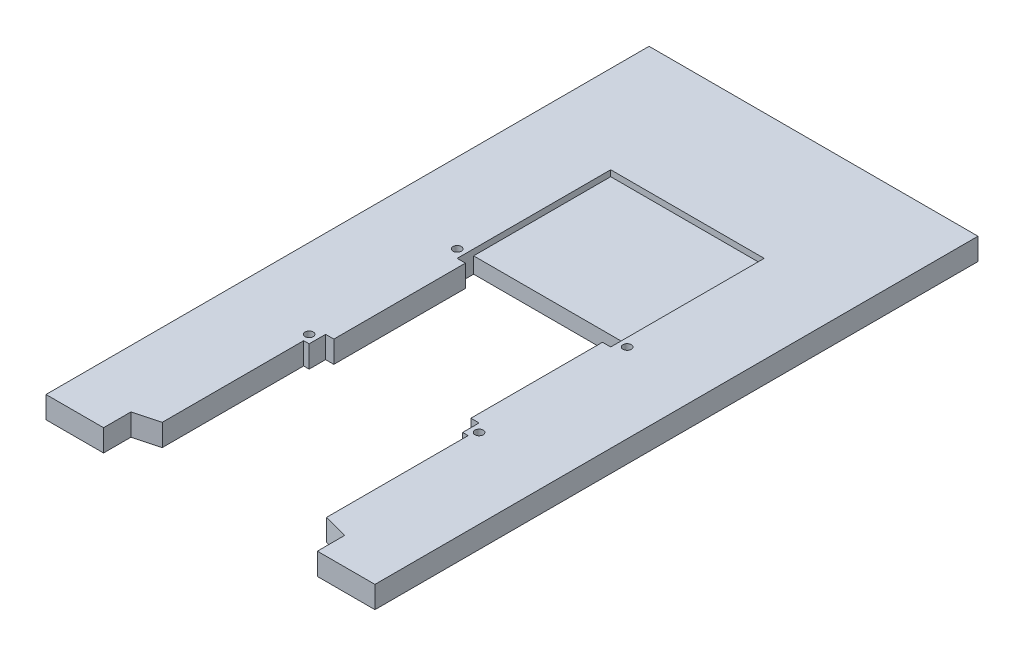
SolidWorks part; units mm, degrees
ref_plane "Front Plane" through (0, 0, 0) normal (0, 0, 1) x (1, 0, 0)
ref_plane "Top Plane" through (0, 0, 0) normal (0, 1, 0) x (1, 0, 0)
ref_plane "Right Plane" through (0, 0, 0) normal (1, 0, 0) x (0, 0, -1)
sketch "Sketch1" plane through (0, 0, 0) normal (0, 1, 0) x (1, 0, 0)
  line L1 (-30, 12.4115) -> (-30, 64)
  line L2 (-28, 124) -> (28, 124)
  line L3 (30, 64) -> (30, 12.4115)
  line L6 (-60, 0) -> (-39, 0)
  line L8 (-28, 70) -> (-28, 64)
  line L9 (-28, 64) -> (-30, 64)
  line L10 (28, 70) -> (28, 64)
  line L11 (28, 64) -> (30, 64)
  line L12 (-28, 70) -> (-25, 70)
  line L13 (-25, 70) -> (-25, 118)
  line L14 (-25, 118) -> (-28, 118)
  line L15 (-28, 118) -> (-28, 124)
  line L16 (28, 124) -> (28, 118)
  line L17 (28, 118) -> (25, 118)
  line L18 (25, 118) -> (25, 70)
  line L19 (25, 70) -> (28, 70)
  line L20 (-39, 0) -> (-39, 10)
  line L21 (-39, 10) -> (-30, 12.4115)
  line L22 (39, 0) -> (39, 10)
  line L23 (39, 10) -> (30, 12.4115)
  line L24 (-60, 0) -> (-60, 220)
  line L25 (-60, 220) -> (60, 220)
  line L26 (60, 220) -> (60, 0)
  line L27 (60, 0) -> (39, 0)
  circle A0 centre (-31, 67) radius 1.5
  circle A1 centre (31, 67) radius 1.5
  circle A2 centre (-31, 121) radius 1.5
  circle A3 centre (31, 121) radius 1.5
  dimension "D17" = 3
  dimension "D2" = 60
  dimension "D3" = 67
  dimension "D5" = 60
  dimension "D6" = 56
  dimension "D7" = 6
  dimension "D8" = 3
  dimension "D9" = 78
  dimension "D10" = 10
  dimension "D11" = 105
  dimension "D12" = 120
  dimension "D13" = 220
  dimension "D14" = 60
  dimension "D16" = 62
  dimension "D18" = 54
  dimension "D19" = 3
  dimension "D20" = 3
extrude "Boss-Extrude1" add sketch "Sketch1" along normal blind 8
sketch "Sketch2" plane through (0, 8, 0) normal (0, 1, 0) x (1, 0, 0)
  line L1 (-28, 124) -> (28, 124)
  line L2 (-28, 124) -> (-28, 174)
  line L3 (-28, 174) -> (28, 174)
  line L4 (28, 124) -> (28, 174)
  dimension "D1" = 50
extrude "Cut-Extrude1" cut sketch "Sketch2" against normal blind 2.2
